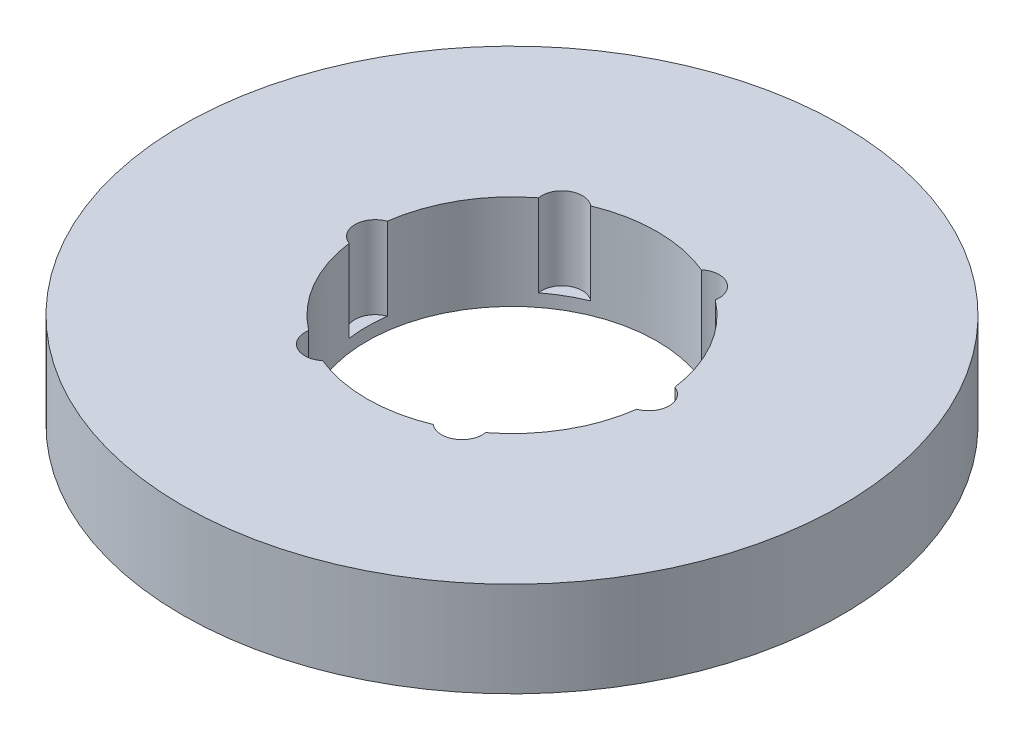
SolidWorks part; units mm, degrees
ref_plane "Front Plane" through (0, 0, 0) normal (0, 0, 1) x (1, 0, 0)
ref_plane "Top Plane" through (0, 0, 0) normal (0, 1, 0) x (1, 0, 0)
ref_plane "Right Plane" through (0, 0, 0) normal (1, 0, 0) x (0, 0, -1)
sketch "Sketch1" plane through (0, 0, 0) normal (0, 1, 0) x (1, 0, 0)
  circle A0 centre (0, 0) radius 62.5
  dimension "FLANGE_OD" = 125
extrude "Boss-Extrude1" add sketch "Sketch1" along normal blind 18
sketch "Sketch2" plane through (0, 0, 0) normal (0, 1, 0) x (1, 0, 0)
  circle A0 centre (0, 0) radius 27.5
  dimension "BORE_D" = 55
extrude "Cut-Extrude1" cut sketch "Sketch2" along normal through all
sketch "Sketch3" plane through (0, 18, 0) normal (0, 1, 0) x (1, 0, 0)
  circle A0 centre (0, 0) radius 25.93 construction
  circle A1 centre (-25.93, 0) radius 3.8594
  dimension "BOLT_D" = 7.7189
  dimension "BOLT_PCD" = 51.86
extrude "Cut-Extrude2" cut sketch "Sketch3" against normal blind 15.605
pattern_circular "CirPattern1" count 6 over 360 about axis through (0, 0, 0) along (0, 1, 0) of "Cut-Extrude2"
